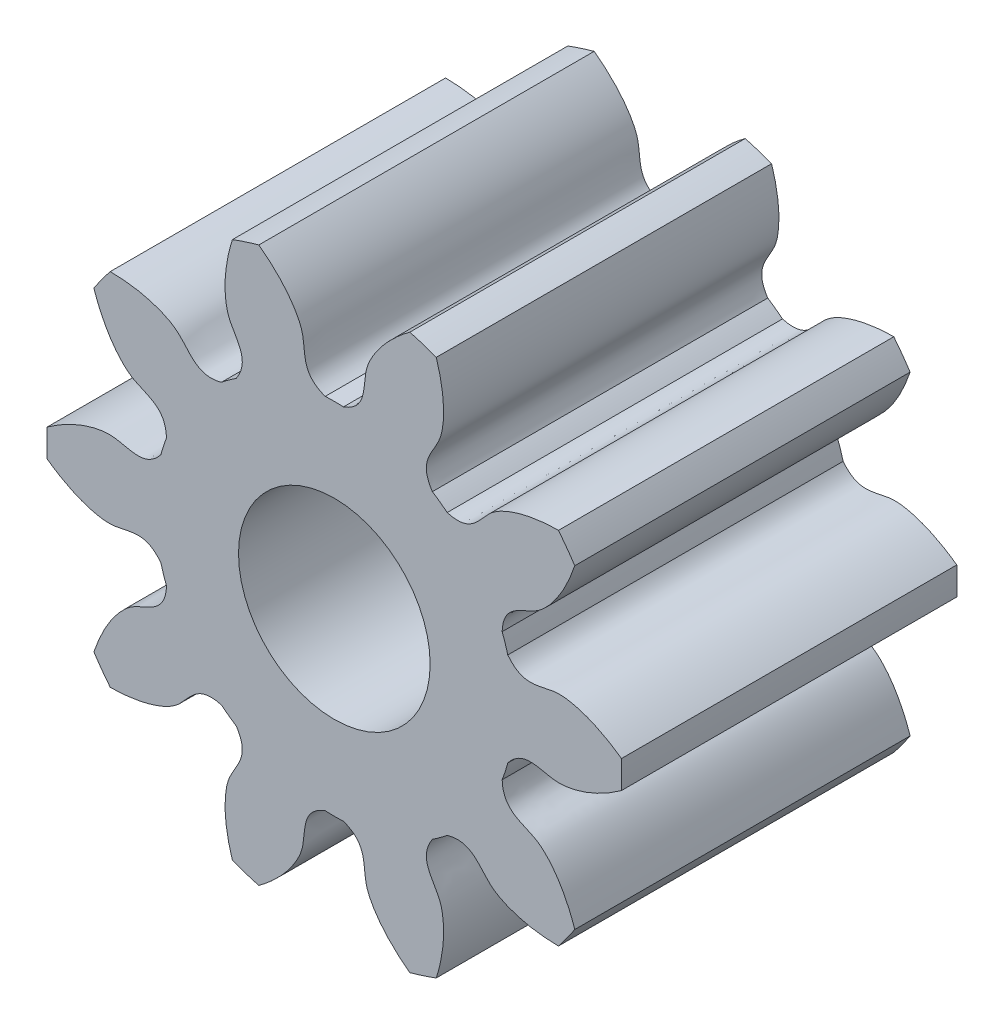
SolidWorks part; units mm, degrees
material "A286 铁基超合金"
ref_plane "前视基准面" through (0, 0, 0) normal (0, 0, 1) x (1, 0, 0)
ref_plane "上视基准面" through (0, 0, 0) normal (0, 1, 0) x (1, 0, 0)
ref_plane "右视基准面" through (0, 0, 0) normal (1, 0, 0) x (0, 0, -1)
sketch "草图1" plane through (0, 0, 0) normal (0, 0, 1) x (1, 0, 0)
  circle A0 centre (0, 0) radius 3
extrude "凸台-拉伸1" add sketch "草图1" along normal blind 3.5
ref_axis "基准轴1" through (0, 0, 3.5) along (0, 0, -1)
sketch "草图2" plane through (0, 0, 0) normal (0, 0, 1) x (1, 0, 0)
  line L0 (0, 0) -> (0, 3) construction
  circle A0 centre (0, 0) radius 3 construction
  arc A1 (0.0952, 1.8726) -> (-0.0952, 1.8726) centre (0, 0) ccw
  arc A2 (2.1268, 3.3471) -> (-2.1268, 3.3471) centre (0, 0) ccw
  spline S0 degree 3 poles (0.0952, 1.8726) (0.3627, 1.9703) (0.2869, 2.1853) (0.3443, 2.3623) (0.3473, 2.3708) (0.3507, 2.38) (0.3546, 2.3901) (0.3591, 2.4009) (0.3642, 2.4126) (0.3699, 2.4249) (0.3763, 2.438) (0.3834, 2.4518) (0.3911, 2.4663) (0.3997, 2.4815) (0.409, 2.4972) (0.4191, 2.5136) (0.4301, 2.5306) (0.4419, 2.5481) (0.4546, 2.5662) (0.4682, 2.5848) (0.4828, 2.6038) (0.4983, 2.6233) (0.5148, 2.6432) (0.5323, 2.6634) (0.5509, 2.684) (0.5705, 2.7049) (0.5911, 2.7261) (0.6129, 2.7476) (0.6358, 2.7692) (0.6598, 2.791) (0.6849, 2.8129) (0.7112, 2.835) (0.7386, 2.8571) (0.7672, 2.8792) (0.7971, 2.9013) (0.8281, 2.9234) (0.8603, 2.9453) (0.8938, 2.9671) (0.9285, 2.9888) (0.9644, 3.0102) (1.0015, 3.0314) (1.0399, 3.0522) (1.0796, 3.0728) (1.1204, 3.0929) (1.1626, 3.1126) (1.2059, 3.1319) (1.2506, 3.1506) (1.2964, 3.1688) (1.3435, 3.1864) (1.3918, 3.2034) (1.4414, 3.2197) (1.4921, 3.2353) (1.5441, 3.2501) (1.5972, 3.2642) (1.6516, 3.2773) (1.7071, 3.2896) (1.7638, 3.301) (1.8216, 3.3114) (1.8805, 3.3208) (1.9405, 3.3291) (2.0227, 3.3388) (2.0849, 3.3443) (2.1268, 3.3471) knots 0 0 0 0 0.201721 0.204697 0.208023 0.211699 0.215726 0.220102 0.224829 0.229906 0.235332 0.241109 0.247237 0.253714 0.260541 0.267719 0.275246 0.283124 0.291352 0.29993 0.308858 0.318136 0.327765 0.337743 0.348072 0.358751 0.36978 0.381158 0.392888 0.404967 0.417396 0.430176 0.443305 0.456785 0.470615 0.484795 0.499325 0.514205 0.529435 0.545016 0.560946 0.577227 0.593858 0.610839 0.62817 0.645851 0.663882 0.682264 0.700995 0.720077 0.739509 0.759291 0.779423 0.799905 0.820737 0.84192 0.863452 0.885335 0.907568 0.930151 0.953084 1 1 1 1
  spline S1 degree 3 poles (-0.0952, 1.8726) (-0.3627, 1.9703) (-0.2869, 2.1853) (-0.3443, 2.3623) (-0.3473, 2.3708) (-0.3507, 2.38) (-0.3546, 2.3901) (-0.3591, 2.4009) (-0.3642, 2.4126) (-0.3699, 2.4249) (-0.3763, 2.438) (-0.3834, 2.4518) (-0.3911, 2.4663) (-0.3997, 2.4815) (-0.409, 2.4972) (-0.4191, 2.5136) (-0.4301, 2.5306) (-0.4419, 2.5481) (-0.4546, 2.5662) (-0.4682, 2.5848) (-0.4828, 2.6038) (-0.4983, 2.6233) (-0.5148, 2.6432) (-0.5323, 2.6634) (-0.5509, 2.684) (-0.5705, 2.7049) (-0.5911, 2.7261) (-0.6129, 2.7476) (-0.6358, 2.7692) (-0.6598, 2.791) (-0.6849, 2.8129) (-0.7112, 2.835) (-0.7386, 2.8571) (-0.7672, 2.8792) (-0.7971, 2.9013) (-0.8281, 2.9234) (-0.8603, 2.9453) (-0.8938, 2.9671) (-0.9285, 2.9888) (-0.9644, 3.0102) (-1.0015, 3.0314) (-1.0399, 3.0522) (-1.0796, 3.0728) (-1.1204, 3.0929) (-1.1626, 3.1126) (-1.2059, 3.1319) (-1.2506, 3.1506) (-1.2964, 3.1688) (-1.3435, 3.1864) (-1.3918, 3.2034) (-1.4414, 3.2197) (-1.4921, 3.2353) (-1.5441, 3.2501) (-1.5972, 3.2642) (-1.6516, 3.2773) (-1.7071, 3.2896) (-1.7638, 3.301) (-1.8216, 3.3114) (-1.8805, 3.3208) (-1.9405, 3.3291) (-2.0227, 3.3388) (-2.0849, 3.3443) (-2.1268, 3.3471) knots 0 0 0 0 0.201721 0.204697 0.208023 0.211699 0.215726 0.220102 0.224829 0.229906 0.235332 0.241109 0.247237 0.253714 0.260541 0.267719 0.275246 0.283124 0.291352 0.29993 0.308858 0.318136 0.327765 0.337743 0.348072 0.358751 0.36978 0.381158 0.392888 0.404967 0.417396 0.430176 0.443305 0.456785 0.470615 0.484795 0.499325 0.514205 0.529435 0.545016 0.560946 0.577227 0.593858 0.610839 0.62817 0.645851 0.663882 0.682264 0.700995 0.720077 0.739509 0.759291 0.779423 0.799905 0.820737 0.84192 0.863452 0.885335 0.907568 0.930151 0.953084 1 1 1 1
extrude "切除-拉伸1" cut sketch "草图2" along normal through all
pattern_circular "阵列(圆周)1" count 10 every 36 about axis through (0, 0, 3.5) along (0, 0, -1) of "切除-拉伸1"
sketch "草图3" plane through (0, 0, 0) normal (0, 0, 1) x (1, 0, 0)
  line L0 (-3, 0) -> (0, 0) construction
  circle A0 centre (0, 0) radius 2.5 construction
  arc A1 (-2.9965, 0.1449) -> (-2.9965, -0.1449) centre (0, 0) ccw construction
  dimension "Dn" = 5
sketch "草图4" plane through (0, 0, 0) normal (0, 0, 1) x (1, 0, 0)
  circle A0 centre (0, 0) radius 1
extrude "切除-拉伸2" cut sketch "草图4" along normal through all
